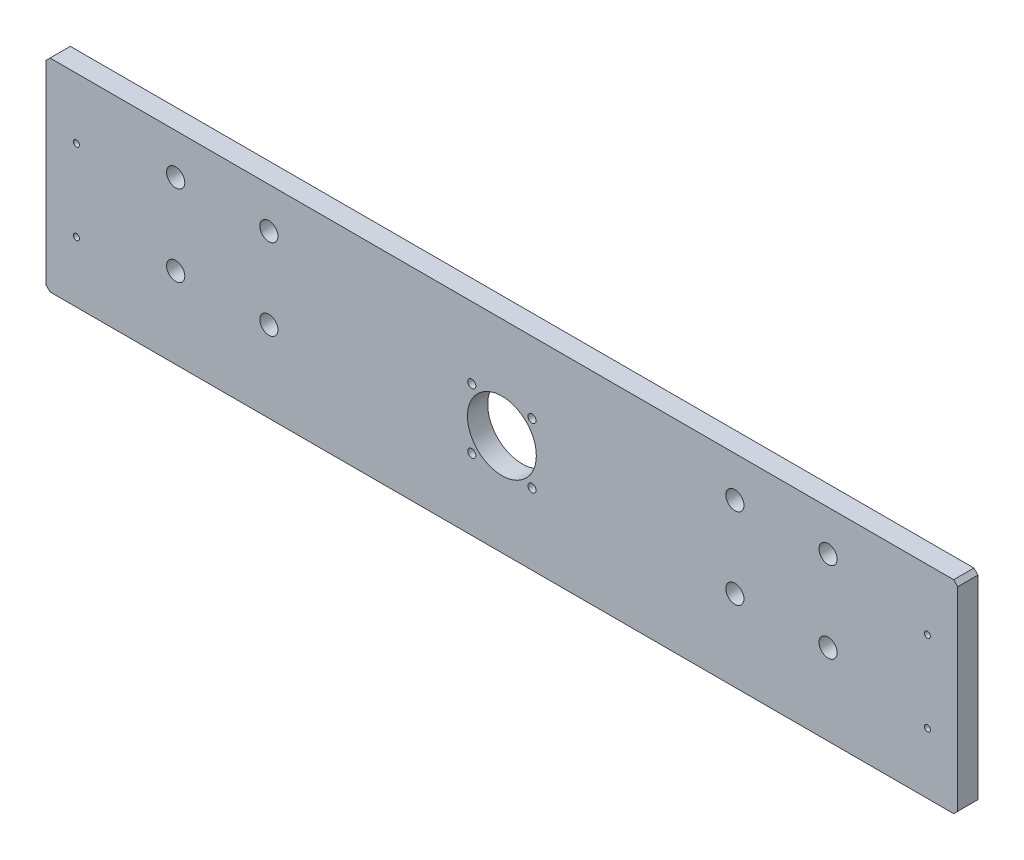
SolidWorks part; units mm, degrees
ref_plane "Piano frontale" through (0, 0, 0) normal (0, 0, 1) x (1, 0, 0)
ref_plane "Piano superiore" through (0, 0, 0) normal (0, 1, 0) x (1, 0, 0)
ref_plane "Piano destro" through (0, 0, 0) normal (1, 0, 0) x (0, 0, -1)
sketch "Schizzo1" plane through (0, 0, 0) normal (0, 0, 1) x (1, 0, 0)
  line L0 (225, 100) -> (225, 0) construction
  line L1 (2, 0) -> (448, 0)
  line L2 (0, 2) -> (0, 98)
  line L3 (2, 100) -> (448, 100)
  line L4 (450, 2) -> (450, 98)
  line L5 (225, 50) -> (199.8765, 75.1235) construction
  line L6 (64, 80) -> (386, 80) construction
  line L7 (225, 50) -> (243.5099, 50) construction
  line L8 (87, 80) -> (87, 40) construction
  line L21 (0, 98) -> (2, 100)
  line L22 (2, 0) -> (0, 2)
  line L23 (448, 0) -> (450, 2)
  line L24 (448, 100) -> (450, 98)
  line L25 (225, 50) -> (450, 50) construction
  circle A0 centre (225, 50) radius 17
  circle A1 centre (225, 50) radius 21 construction
  circle A2 centre (239.8492, 64.8492) radius 2
  circle A3 centre (110, 40) radius 4.5
  circle A4 centre (239.8492, 35.1508) radius 2
  circle A5 centre (210.1508, 35.1508) radius 2
  circle A6 centre (110, 80) radius 4.5
  circle A7 centre (386, 40) radius 4.5
  circle A8 centre (64, 40) radius 4.5
  circle A9 centre (64, 80) radius 4.5
  circle A10 centre (340, 40) radius 4.5
  circle A11 centre (15, 30) radius 1.5
  circle A12 centre (435, 30) radius 1.5
  circle A13 centre (210.1508, 64.8492) radius 2
  circle A14 centre (340, 80) radius 4.5
  circle A15 centre (386, 80) radius 4.5
  circle A17 centre (435, 70) radius 1.5
  circle A18 centre (15, 70) radius 1.5
  point P0 (0, 0)
  point P1 (450, 100)
  point P2 (0, 100)
  point P3 (450, 0)
  point P13 (210.1508, 64.8492)
  point P14 (239.8492, 64.8492)
  point P15 (210.1508, 35.1508)
  point P17 (239.8492, 35.1508)
  dimension "D4" = 34
  dimension "D10" = 64
  dimension "D15" = 3
  dimension "D17" = 4
  dimension "D8" = 42
  dimension "D1" = 100
  dimension "D2" = 450
  dimension "D3" = 50
  dimension "D5" = 45
  dimension "D6" = 20
  dimension "D7" = 40
  dimension "D9" = 23
  dimension "D14" = 30
  dimension "D16" = 15
extrude "Estrusione-Estrusione1" add sketch "Schizzo1" against normal blind 10
